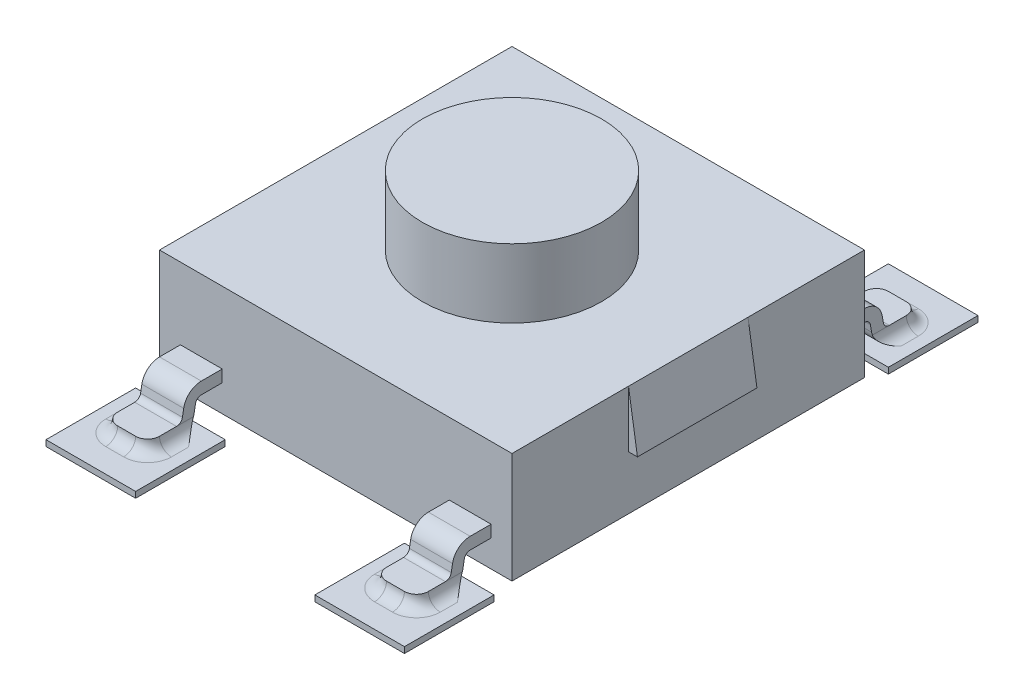
SolidWorks part; units mm, degrees
material "PA Type 6"
ref_plane "Front Plane" through (0, 0, 0) normal (0, 0, 1) x (1, 0, 0)
ref_plane "Top Plane" through (0, 0, 0) normal (0, 1, 0) x (1, 0, 0)
ref_plane "Right Plane" through (0, 0, 0) normal (1, 0, 0) x (0, 0, -1)
sketch "Sketch1" plane through (0, 0, 0) normal (0, 1, 0) x (1, 0, 0)
  line L0 (0, -55) -> (0, 55) construction
  line L1 (2.95, -2.95) -> (-2.95, -2.95)
  line L2 (2.95, -2.95) -> (2.95, 2.95)
  line L3 (2.95, 2.95) -> (-2.95, 2.95)
  line L4 (-2.95, -2.95) -> (-2.95, 2.95)
  line L5 (-55, 0) -> (55, 0) construction
  dimension "D1" = 5.9
  dimension "D2" = 2.95
  dimension "D3" = 2.95
extrude "Boss-Extrude1" add sketch "Sketch1" along normal blind 1.85
sketch "Sketch2" plane through (0, 0, 0) normal (0, 0, 1) x (1, 0, 0)
  line L0 (-2.95, 1.85) -> (-3.1, 0.9)
  line L1 (-3.1, 0.9) -> (3.1, 0.9)
  line L2 (3.1, 0.9) -> (2.95, 1.85)
  line L3 (2.95, 1.85) -> (-2.95, 1.85)
  line L4 (0, -1.0175) -> (0, 1.0175) construction
  dimension "D1" = 0.95
  dimension "D2" = 6.2
  dimension "D3" = 3.1
extrude "Boss-Extrude2" add sketch "Sketch2" along normal mid plane 2
ref_plane "Plane1" through (2.25, 0, 0) normal (1, 0, 0) x (0, 0, -1)
sketch "Sketch3" plane through (2.25, 0, 0) normal (1, 0, 0) x (0, 0, -1)
  line L0 (-4.2, 0.1) -> (-3.715, 0.1)
  line L1 (-3.518, 0.2653) -> (-3.497, 0.3847)
  line L2 (-3.3, 0.55) -> (3.3, 0.55)
  line L3 (3.497, 0.3847) -> (3.518, 0.2653)
  line L4 (3.715, 0.1) -> (4.2, 0.1)
  line L5 (3.245, 0) -> (-3.245, 0) construction
  line L6 (0, 1.0175) -> (0, -1.0175) construction
  arc A0 (3.3, 0.55) -> (3.497, 0.3847) centre (3.3, 0.35) cw
  arc A1 (3.518, 0.2653) -> (3.715, 0.1) centre (3.715, 0.3) ccw
  arc A2 (-3.715, 0.1) -> (-3.518, 0.2653) centre (-3.715, 0.3) ccw
  arc A3 (-3.497, 0.3847) -> (-3.3, 0.55) centre (-3.3, 0.35) cw
  dimension "D6" = 0.2
  dimension "D7" = 0.2
  dimension "D1" = 0.1
  dimension "D2" = 0.55
  dimension "D3" = 10
  dimension "D4" = 10
  dimension "D5" = 4.2
  dimension "D8" = 3.3
  dimension "D9" = 3.3
extrude "Extrude-Thin1" add sketch "Sketch3" along normal mid plane 0.7 thin thin type mid plane wall 0.2
fillet "Fillet1" radius 0.2 4 edges at (1.9, 0.1, -4.2) (2.6, 0.1, -4.2) (1.9, 0.1, 4.2) (2.6, 0.1, 4.2)
pattern_linear "LPattern1" count 2 spacing 4.5 along (-1, 0, 0) of "Fillet1", "Extrude-Thin1"
sketch "Sketch4" plane through (0, 0, 0) normal (0, 1, 0) x (1, 0, 0)
  line L0 (0, -1.0175) -> (0, 1.0175) construction
  line L1 (-3, 4.8) -> (-1.5, 4.8)
  line L2 (-3, 4.8) -> (-3, 3.3)
  line L3 (-3, 3.3) -> (-1.5, 3.3)
  line L4 (-1.5, 4.8) -> (-1.5, 3.3)
  line L5 (1.5, 4.8) -> (3, 4.8)
  line L6 (1.5, 4.8) -> (1.5, 3.3)
  line L7 (1.5, 3.3) -> (3, 3.3)
  line L8 (3, 4.8) -> (3, 3.3)
  line L9 (1.5, -3.3) -> (3, -3.3)
  line L10 (1.5, -3.3) -> (1.5, -4.8)
  line L11 (1.5, -4.8) -> (3, -4.8)
  line L12 (3, -3.3) -> (3, -4.8)
  line L13 (-3, -3.3) -> (-1.5, -3.3)
  line L14 (-3, -3.3) -> (-3, -4.8)
  line L15 (-3, -4.8) -> (-1.5, -4.8)
  line L16 (-1.5, -3.3) -> (-1.5, -4.8)
  line L17 (-0.75, 4.8) -> (0.75, 4.8)
  line L18 (-0.75, 4.8) -> (-0.75, 3.3)
  line L19 (-0.75, 3.3) -> (0.75, 3.3)
  line L20 (0.75, 4.8) -> (0.75, 3.3)
  line L21 (-1.0175, 0) -> (1.0175, 0) construction
  dimension "D1" = 1.5
  dimension "D2" = 4.5
  dimension "D3" = 1.5
  dimension "D4" = 0.75
  dimension "D5" = 3.3
  dimension "D6" = 3.3
extrude "Boss-Extrude3" add sketch "Sketch4" against normal blind 0.1
fillet "Fillet2" radius 0.2 20 edges at (1.9, 0, -3.8575) (2.6, 0, -3.8575) (2.5414, 0, -4.1414) (2.25, 0, -4.2) (-1.9, 0, -3.8575) (-1.9586, 0, -4.1414) (-2.25, 0, -4.2) (-2.5414, 0, -4.1414) (2.6, 0, 3.8575) (2.5414, 0, 4.1414) (1.9, 0, 3.8575) (1.9586, 0, 4.1414) (-1.9, 0, 3.8575) (-1.9586, 0, 4.1414) (-2.25, 0, 4.2) (-2.6, 0, 3.8575) (1.9586, 0, -4.1414) (-2.6, 0, -3.8575) (2.25, 0, 4.2) (-2.5414, 0, 4.1414)
sketch "Sketch5" plane through (0, 1.85, 0) normal (0, 1, 0) x (1, 0, 0)
  circle A0 centre (0, 0) radius 1.5
  dimension "D1" = 3
extrude "Boss-Extrude4" add sketch "Sketch5" along normal blind 1.15
